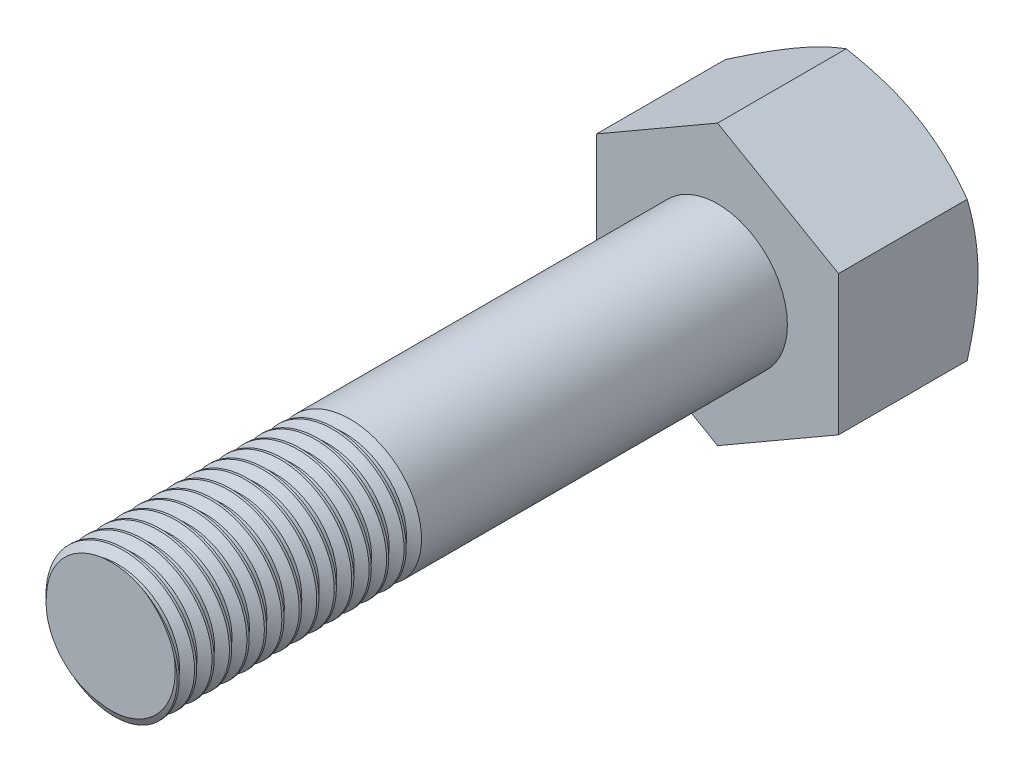
SolidWorks part; units mm, degrees
ref_plane "Front Plane" through (0, 0, 0) normal (0, 0, 1) x (1, 0, 0)
ref_plane "Top Plane" through (0, 0, 0) normal (0, 1, 0) x (1, 0, 0)
ref_plane "Right Plane" through (0, 0, 0) normal (1, 0, 0) x (0, 0, -1)
sketch "Sketch1" plane through (0, 0, 0) normal (0, 0, 1) x (1, 0, 0)
  line L1 (0, 24) -> (-20.7846, 12)
  line L2 (-20.7846, 12) -> (-20.7846, -12)
  line L3 (-20.7846, -12) -> (0, -24)
  line L4 (0, -24) -> (20.7846, -12)
  line L5 (20.7846, -12) -> (20.7846, 12)
  line L6 (20.7846, 12) -> (0, 24)
  circle A0 centre (0, 0) radius 20.7846 construction
  dimension "D1" = 48
extrude "Boss-Extrude2" add sketch "Sketch1" along normal blind 24
sketch "Sketch3" plane through (0, 0, 24) normal (0, 0, 1) x (1, 0, 0)
  circle A0 centre (0, 0) radius 12
  dimension "D1" = 24
extrude "Boss-Extrude3" add sketch "Sketch3" along normal blind 105
sketch "Sketch4" plane through (0, 0, 0) normal (1, 0, 0) x (0, 0, -1)
  arc A0 (-129.0387, -11.9722) -> (-129, -12) centre (-120.4035, 0) ccw
sketch "Sketch5" plane through (0, 0, 0) normal (0, 0, -1) x (-1, 0, 0)
  circle A0 centre (0, 0) radius 20.7202
extrude "Cut-Extrude1" cut sketch "Sketch5" against normal blind 34 draft 60 flip side to cut
thread "Thread1" pitch 3 method cut profile "Thread Profile1" start angle 0, offset 10, length 50, pitch 3, diameter 24
ref_plane "Plane1" through (-12, 0, 139) normal (0, -1, 0) x (-1, 0, 0)
sketch "Thread Profile1" plane through (-12, 0, 139) normal (0, -1, 0) x (-1, 0, 0)
  line L0 (0, 0) -> (0, 3) construction
  line L11 (0, 0) -> (0, 2.625)
  line L12 (0, 2.625) -> (-1.6238, 1.6875)
  line L13 (-1.6238, 1.6875) -> (-1.6238, 0.9375)
  line L15 (-1.6238, 0.9375) -> (0, 0)
  line L17 (-1.6238, 1.3125) -> (0, 1.3125) construction
  point P2 (0, 0)
  dimension "Pitch" = 3
  dimension "Profile_Angle" = 60
  dimension "Profile_Land" = 0.75
  dimension "Profile_Height" = 1.6238
